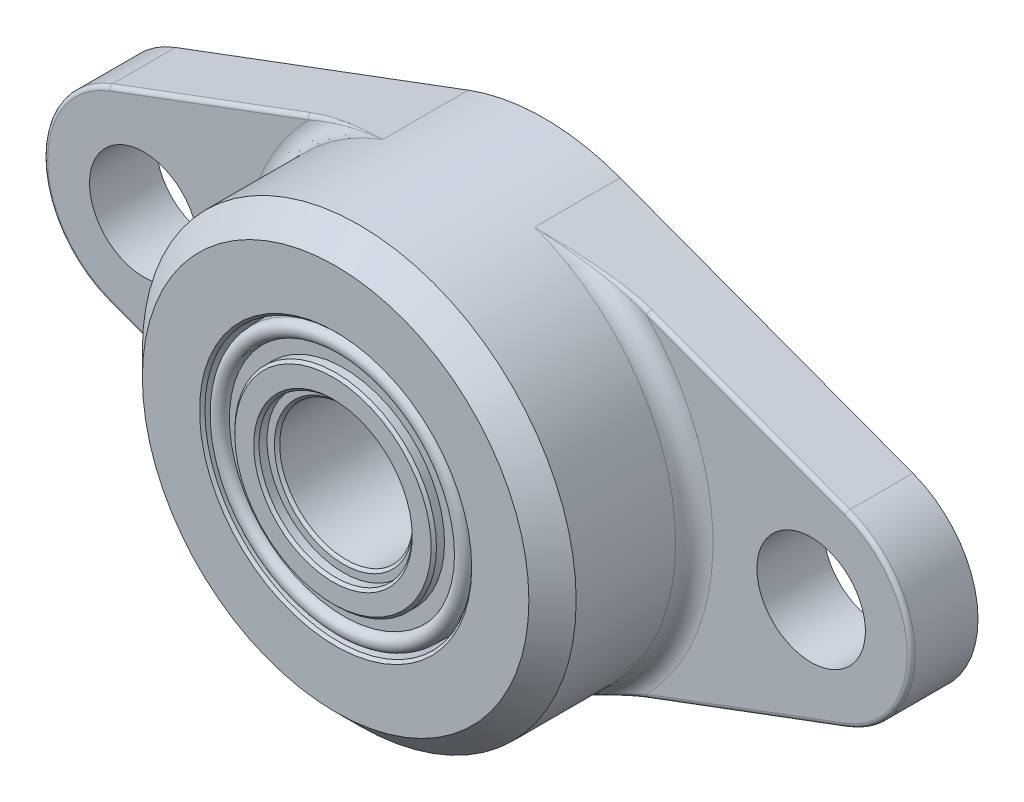
SolidWorks part; units mm, degrees
ref_plane "Front Plane" through (0, 0, 0) normal (0, 0, 1) x (1, 0, 0)
ref_plane "Top Plane" through (0, 0, 0) normal (0, 1, 0) x (1, 0, 0)
ref_plane "Right Plane" through (0, 0, 0) normal (1, 0, 0) x (0, 0, -1)
sketch "Sketch1" plane through (0, 0, 0) normal (0, 0, 1) x (1, 0, 0)
  line L0 (-31.75, 0) -> (31.75, 0) construction
  line L1 (0, 20.6375) -> (0, -20.6375) construction
  line L2 (-35.0838, 8.9225) -> (-7.2231, 19.3322)
  line L3 (7.2231, 19.3322) -> (35.0838, 8.9225)
  line L4 (35.0838, -8.9225) -> (7.2231, -19.3322)
  line L5 (-35.0838, -8.9225) -> (-7.2231, -19.3322)
  line L6 (-41.275, 0) -> (41.275, 0) construction
  line L7 (4.4811, 4.4811) -> (14.5929, 14.5929) construction
  circle A0 centre (-31.75, 0) radius 5.1594
  circle A1 centre (31.75, 0) radius 5.1594
  circle A2 centre (0, 0) radius 20.6375
  arc A3 (-35.0838, 8.9225) -> (-35.0838, -8.9225) centre (-31.75, 0) ccw
  arc A4 (35.0838, -8.9225) -> (35.0838, 8.9225) centre (31.75, 0) ccw
  circle A5 centre (0, 0) radius 6.3373
  circle A6 centre (0, 0) radius 12.6929 construction
  point P23 (8.9753, 8.9753)
  point P24 (0, 12.6929)
  point P25 (0, 6.3373)
  dimension "Mounting Hole" = 10.3187
  dimension "ID" = 12.6746
  dimension "D4" = 25.3859
  dimension "Mounting Center" = 63.5
  dimension "Height" = 41.275
  dimension "Length" = 82.55
  dimension "D2" = 45
  dimension "D3" = 14.3002
  dimension "D1" = 6.3556
sketch "Sketch2" plane through (0, 0, 0) normal (1, 0, 0) x (0, 0, -1)
  line L0 (9.9219, 0) -> (-9.9219, 0) construction
  point P2 (3.5719, 0)
  point P4 (9.9219, 0)
  dimension "Width" = 19.8438
  dimension "flange thickness" = 6.35
  dimension "Bearing Width" = 19.8438
sketch "Sketch3" plane through (0, 0, 0) normal (0, 0, 1) x (1, 0, 0)
  line L0 (-35.0838, 8.9225) -> (-7.2231, 19.3322) construction
  line L1 (7.2231, 19.3322) -> (35.0837, 8.9225) construction
  line L2 (35.0837, -8.9225) -> (7.2231, -19.3322) construction
  line L3 (-35.0838, -8.9225) -> (-7.2231, -19.3322) construction
  line L4 (-35.0838, 8.9225) -> (-7.2231, 19.3322)
  line L5 (7.2231, 19.3322) -> (35.0837, 8.9225)
  line L6 (35.0837, -8.9225) -> (7.2231, -19.3322)
  line L7 (-35.0838, -8.9225) -> (-7.2231, -19.3322)
  arc A0 (-35.0838, 8.9225) -> (-35.0838, -8.9225) centre (-31.75, 0) ccw construction
  circle A1 centre (-31.75, 0) radius 5.1594 construction
  circle A2 centre (0, 0) radius 20.6375 construction
  circle A3 centre (31.75, 0) radius 5.1594 construction
  arc A4 (35.0837, -8.9225) -> (35.0837, 8.9225) centre (31.75, 0) ccw construction
  arc A5 (-35.0838, 8.9225) -> (-35.0838, -8.9225) centre (-31.75, 0) ccw
  circle A6 centre (-31.75, 0) radius 5.1594
  arc A7 (-7.2231, -19.3322) -> (7.2231, -19.3322) centre (0, 0) ccw
  circle A8 centre (31.75, 0) radius 5.1594
  arc A9 (35.0837, -8.9225) -> (35.0837, 8.9225) centre (31.75, 0) ccw
  circle A10 centre (0, 0) radius 12.6929 construction
  circle A11 centre (0, 0) radius 12.6929
  arc A12 (7.2231, 19.3322) -> (-7.2231, 19.3322) centre (0, 0) ccw
extrude "Boss-Extrude1" add sketch "Sketch3" along normal up to vertex (-3.5719 mm away) from vertex at -9.9219 starting at point (0, 0, -9.9219)
sketch "Sketch4" plane through (0, 0, -3.5719) normal (0, 0, 1) x (1, 0, 0)
  circle A0 centre (0, 0) radius 20.6375 construction
  circle A1 centre (0, 0) radius 12.6929 construction
  circle A2 centre (0, 0) radius 20.6375
  circle A3 centre (0, 0) radius 12.6929
extrude "Boss-Extrude2" add sketch "Sketch4" along normal up to vertex
chamfer "Chamfer1" distance 0.254 angle 45 2 edges at (12.6929, 0, 9.9219) (12.6929, 0, -9.9219)
fillet "Fillet1" radius 1.778 2 edges
fillet "Fillet2" radius 0.381 10 edges at (12.0878, 17.5146, -3.1628) (41.275, 0, -3.5719) (-12.0878, 17.5146, -3.1628) (-41.275, 0, -3.5719) (-12.0878, -17.5146, -3.1628) (12.0878, -17.5146, -3.1628)
chamfer "Chamfer2" distance 2.249 angle 45 1 edges at (20.6375, 0, 9.9219)
sketch "Sketch5" plane through (0, 0, 0) normal (1, 0, 0) x (0, 0, -1)
  line L0 (-9.9219, 6.3373) -> (9.9219, 6.3373)
  line L1 (-9.9219, 6.3373) -> (-9.9219, 12.6929)
  line L2 (-9.9219, 12.6929) -> (9.9219, 12.6929)
  line L3 (9.9219, 12.6929) -> (9.9219, 6.3373)
  line L4 (-9.9219, 0) -> (9.9219, 0) construction
  dimension "D1" = 19.8438
sketch "Sketch6" plane through (0, 0, 0) normal (1, 0, 0) x (0, 0, -1)
  line L0 (0, 12.6929) -> (-9.1967, 12.3718)
  line L1 (-9.1599, 10.8695) -> (-9.1599, 9.599)
  line L2 (-9.1599, 9.599) -> (-10.1759, 9.599)
  line L3 (-10.1759, 9.599) -> (-10.1759, 7.2879)
  line L4 (-9.1599, 6.3373) -> (-9.1599, 7.2879)
  line L5 (-9.1599, 7.2879) -> (-10.1759, 7.2879)
  line L6 (-9.9219, 6.3373) -> (9.9219, 6.3373) construction
  line L7 (-9.9219, 6.3373) -> (-9.9219, 12.6929) construction
  line L8 (-9.9219, 18.3885) -> (-9.9219, -18.3885) construction
  line L9 (-9.9219, 12.6929) -> (9.9219, 12.6929) construction
  line L10 (7.6359, 6.3373) -> (7.6359, 7.2879)
  line L11 (7.6359, 7.2879) -> (8.6519, 7.2879)
  line L12 (8.6519, 7.2879) -> (8.6519, 9.599)
  line L13 (8.6519, 9.599) -> (6.1119, 9.599)
  line L14 (6.1119, 9.599) -> (6.1119, 10.8695)
  line L15 (6.1119, 10.8695) -> (9.9219, 10.8695)
  line L16 (9.9219, 12.6929) -> (9.9219, 6.3373) construction
  line L17 (9.9219, 10.8695) -> (9.9219, 12.6929)
  line L18 (-9.1599, 6.3373) -> (7.6359, 6.3373)
  line L19 (0, 12.6929) -> (9.9219, 12.6929)
  line L20 (-9.9219, 0) -> (9.9219, 0) construction
  arc A0 (-9.1967, 12.3718) -> (-9.1599, 10.8695) centre (-9.1705, 11.6209) ccw
  dimension "D1" = 0.254
  dimension "D2" = 0.762
  dimension "D3" = 2
  dimension "D4" = 6.3556
  dimension "D5" = 2.3111
  dimension "D6" = 14.5758
  dimension "D7" = 1.5022
  dimension "D8" = 1.27
  dimension "D9" = 2.54
revolve "Revolve1" add sketch "Sketch6" angle 360 about L20
chamfer "Chamfer3" distance 0.254 angle 45 6 edges at (7.2879, 0, -8.6519) (9.599, 0, -8.6519) (9.599, 0, 10.1759) (7.2879, 0, 10.1759) (6.3373, 0, 9.1599) (6.3373, 0, -7.6359)
sketch "Sketch7" plane through (0, 0, -9.9219) normal (0, 0, -1) x (-1, 0, 0)
  line L0 (-41.275, 0) -> (41.275, 0) construction
  arc A0 (-35.0837, 8.9225) -> (-35.0837, -8.9225) centre (-31.75, 0) ccw construction
  arc A1 (35.0838, -8.9225) -> (35.0838, 8.9225) centre (31.75, 0) ccw construction
equation "\"D1@Chamfer2\"=(\"Width@Sketch2\"-\"flange thickness@Sketch2\")/6"
equation "\"D1@Sketch1\"=\"D3@Sketch1\"/2.25"
equation "\"D1@Sketch5\"=\"Bearing Width@Sketch2\""
equation "\"D5@Sketch6\"=\"D4@Sketch6\"/2.75"
equation "\"D6@Sketch6\"=\"ID@Sketch1\"*1.15"
equation "\"D7@Sketch6\"=\"D5@Sketch6\"*.65"
